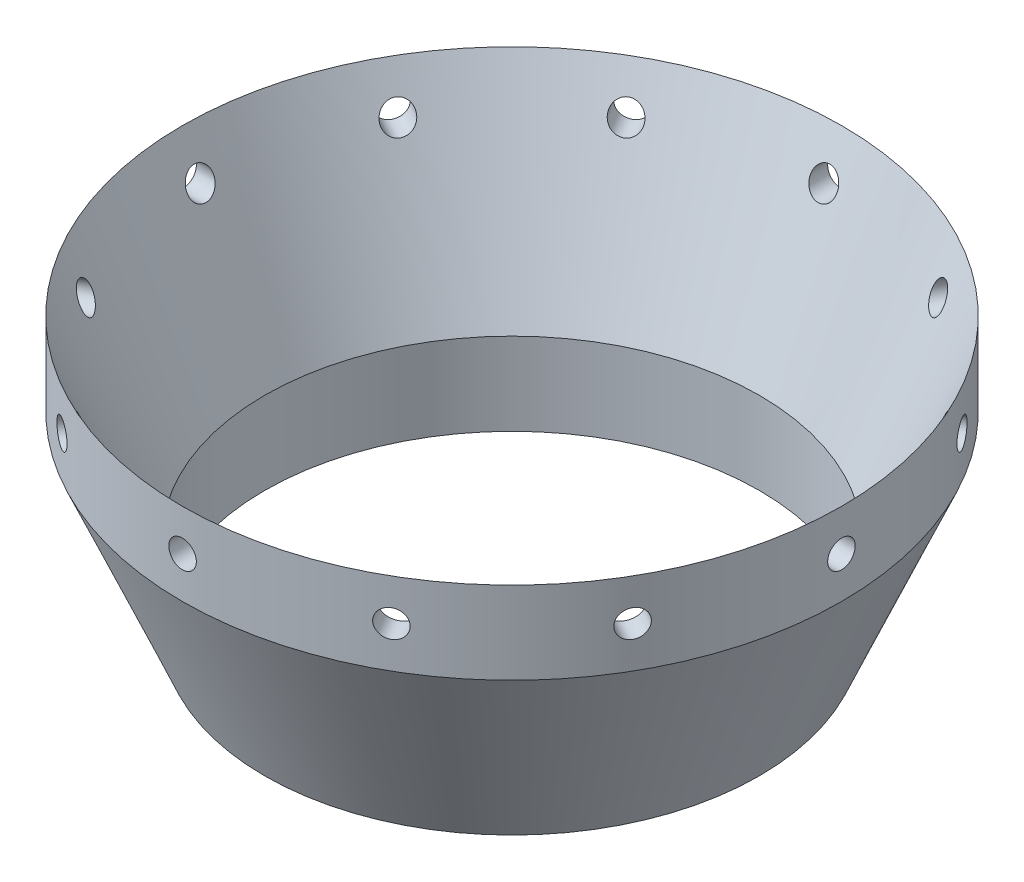
SolidWorks part; units mm, degrees
material "2024-T3"
ref_plane "Front Plane" through (0, 0, 0) normal (0, 0, 1) x (1, 0, 0)
ref_plane "Top Plane" through (0, 0, 0) normal (0, 1, 0) x (1, 0, 0)
ref_plane "Right Plane" through (0, 0, 0) normal (1, 0, 0) x (0, 0, -1)
sketch "Sketch1" plane through (0, 0, 0) normal (0, 0, 1) x (1, 0, 0)
  line L0 (0, 0) -> (0, 220.7687) construction
  line L1 (-57.15, 180.256) -> (-57.15, 199.306)
  line L2 (-57.15, 199.306) -> (-76.2, 243.756)
  line L3 (-76.2, 243.756) -> (-76.2, 224.706)
  line L4 (-76.2, 224.706) -> (-57.15, 180.256)
  dimension "D1" = 57.15
  dimension "D2" = 76.2
  dimension "D3" = 44.45
  dimension "D4" = 19.05
  dimension "D5" = 19.05
revolve "Revolve1" add sketch "Sketch1" angle 360 about L0
sketch "Sketch2" plane through (0, 0, 0) normal (0, 0, 1) x (1, 0, 0)
  line L0 (0, 235.8035) -> (0, 187.481) construction
  line L1 (76.2, 224.706) -> (-76.2, 224.706) construction
  circle A0 centre (0, 234.231) radius 3.175
  dimension "D1" = 9.525
extrude "Cut-Extrude1" cut sketch "Sketch2" against normal through all
ref_axis "Axis1" through (0, 235.8035, 0) along (0, -1, 0)
pattern_circular "CirPattern1" count 12 over 360 about axis through (0, 235.8035, 0) along (0, -1, 0) of "Cut-Extrude1"
